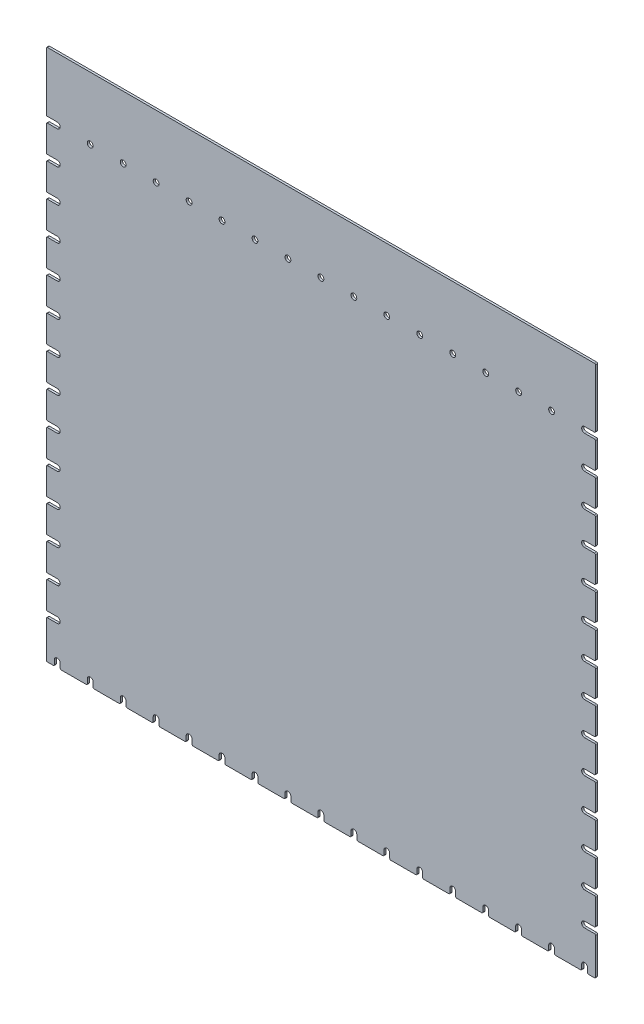
SolidWorks part; units mm, degrees
material "AISI 1045 Steel, cold drawn"
ref_plane "Front Plane" through (0, 0, 0) normal (0, 0, 1) x (1, 0, 0)
ref_plane "Top Plane" through (0, 0, 0) normal (0, 1, 0) x (1, 0, 0)
ref_plane "Right Plane" through (0, 0, 0) normal (1, 0, 0) x (0, 0, -1)
sketch "Sketch1" plane through (0, 0, 0) normal (0, 0, 1) x (1, 0, 0)
  line L1 (250, -242.265) -> (-250, -242.265)
  line L2 (250, -242.265) -> (250, 242.265)
  line L3 (250, 242.265) -> (-250, 242.265)
  line L4 (-250, -242.265) -> (-250, 242.265)
  line L5 (250, -242.265) -> (-250, 242.265) construction
  line L6 (250, 242.265) -> (-250, -242.265) construction
  point P0 (0, 0)
  dimension "D1" = 500
  dimension "D2" = 484.53
extrude "Boss-Extrude1" add sketch "Sketch1" along normal mid plane 2
hole_wizard "M5 Clearance Hole2" positions "Sketch2" profile "Sketch3" hole size "M5" standard "ANSI Metric"
sketch "Sketch2" plane through (0, 0, 1) normal (0, 0, 1) x (1, 0, 0)
  line L1 (240, -237.265) -> (-240, -237.265)
  line L2 (240, -237.265) -> (240, 185.265)
  line L3 (240, 185.265) -> (-240, 185.265)
  line L4 (-240, -237.265) -> (-240, 185.265)
  line L5 (240, -237.265) -> (-240, 185.265) construction
  line L6 (240, 185.265) -> (-240, -237.265) construction
  line L7 (-250, -242.265) -> (250, -242.265) construction
  line L8 (-250, 242.265) -> (-250, -242.265) construction
  line L9 (0, -26) -> (0, -237.265) construction
  point P137 (-240, -237.265)
  point P142 (0, -26)
  dimension "D1" = 5
  dimension "D2" = 10
  dimension "D3" = 427.53
sketch "Sketch3" plane through (-240, -237.265, 1) normal (1, 0, 0) x (0, -1, 0)
  line L0 (0, 0) -> (0, 9.5923)
  line L1 (0, 9.5923) -> (2.65, 8)
  line L2 (2.65, 8) -> (2.65, 0)
  line L5 (2.65, 0) -> (0, 0)
  line L10 (0, 9.5923) -> (-2.65, 8) construction
  line L11 (0, -6.35) -> (0, 107.95) construction
  dimension "Hole Dia." = 5.3
  dimension "Hole Depth" = 8
  dimension "Drill Angle" = 118
sketch "Sketch4" plane through (0, 0, 1) normal (0, 0, 1) x (1, 0, 0)
  line L0 (-242.65, -237.265) -> (-242.65, -242.265)
  line L1 (-250, -242.265) -> (250, -242.265) construction
  line L2 (-242.65, -242.265) -> (-237.35, -242.265)
  line L3 (-237.35, -242.265) -> (-237.35, -237.265)
  circle A0 centre (-240, -237.265) radius 2.65 construction
  arc A1 (-242.65, -237.265) -> (-237.35, -237.265) centre (-240, -237.265) ccw
  point P9 (-242.1, -237.265)
  point P10 (-237.9, -237.265)
extrude "Cut-Extrude1" cut sketch "Sketch4" against normal up to surface (2 mm away) up to face at (-237.35, -237.265, -1)
pattern_linear "LPattern1" count 17 spacing 30 along (1, 0, 0) of "Cut-Extrude1", "M5 Clearance Hole2"
fillet "Fillet1" radius 1 34 edges at (-182.65, -242.265, 0) (-177.35, -242.265, 0) (-152.65, -242.265, 0) (-147.35, -242.265, 0) (-122.65, -242.265, 0) (-117.35, -242.265, 0) (-92.65, -242.265, 0) (-87.35, -242.265, 0) (-62.65, -242.265, 0) (-57.35, -242.265, 0) (-32.65, -242.265, 0) (-27.35, -242.265, 0) (-2.65, -242.265, 0) (2.65, -242.265, 0) (27.35, -242.265, 0) (32.65, -242.265, 0) (57.35, -242.265, 0) (62.65, -242.265, 0) (87.35, -242.265, 0) (92.65, -242.265, 0) (117.35, -242.265, 0) (122.65, -242.265, 0) (147.35, -242.265, 0) (152.65, -242.265, 0) (177.35, -242.265, 0) (182.65, -242.265, 0) (207.35, -242.265, 0) (212.65, -242.265, 0) (237.35, -242.265, 0) (242.65, -242.265, 0) (-237.35, -242.265, 0) (-212.65, -242.265, 0) (-207.35, -242.265, 0) (-242.65, -242.265, 0)
hole_wizard "M5 Clearance Hole1" positions "Sketch5" profile "Sketch6" hole size "M5" standard "ANSI Metric"
sketch "Sketch5" plane through (0, 0, 1) normal (0, 0, 1) x (1, 0, 0)
  point P0 (-240, 185.265)
sketch "Sketch6" plane through (-240, 185.265, 1) normal (1, 0, 0) x (0, -1, 0)
  line L0 (0, 0) -> (0, 9.5923)
  line L1 (0, 9.5923) -> (2.65, 8)
  line L2 (2.65, 8) -> (2.65, 0)
  line L5 (2.65, 0) -> (0, 0)
  line L10 (0, 9.5923) -> (-2.65, 8) construction
  line L11 (0, -6.35) -> (0, 107.95) construction
  dimension "Hole Dia." = 5.3
  dimension "Hole Depth" = 8
  dimension "Drill Angle" = 118
pattern_linear "LPattern2" count 17 spacing 30 along (1, 0, 0) of "M5 Clearance Hole1"
sketch "Sketch7" plane through (0, 0, 1) normal (0, 0, 1) x (1, 0, 0)
  line L0 (-240, 187.915) -> (-250, 187.915)
  line L1 (-250, 242.265) -> (-250, -242.265) construction
  line L2 (-250, 187.915) -> (-250, 182.615)
  line L3 (-250, 182.615) -> (-240, 182.615)
  circle A0 centre (-240, 185.265) radius 2.65 construction
  arc A1 (-240, 187.915) -> (-240, 182.615) centre (-240, 185.265) ccw
  point P6 (-240, 187.915)
  point P9 (-240, 182.615)
  point P10 (0, 0)
extrude "Cut-Extrude2" cut sketch "Sketch7" against normal up to surface (2 mm away) up to face at (-207.35, 185.265, -1)
pattern_linear "LPattern3" count 14 spacing 30 along (0, -1, 0) of "M5 Clearance Hole1", "Cut-Extrude2"
mirror "Mirror1" about plane through (0, 0, 0) normal (1, 0, 0) of "LPattern3"
fillet "Fillet2" radius 1 60 edges at (250, 187.915, 0) (250, 242.265, 0) (-250, 242.265, 0) (-250, 182.615, 0) (-250, 157.915, 0) (-250, 152.615, 0) (-250, 127.915, 0) (-250, 122.615, 0) (-250, 97.915, 0) (-250, 92.615, 0) (-250, 67.915, 0) (-250, 62.615, 0) (-250, 37.915, 0) (-250, 32.615, 0) (-250, 7.915, 0) (-250, 2.615, 0) (-250, -22.085, 0) (-250, -27.385, 0) (-250, -52.085, 0) (-250, -57.385, 0) (-250, -82.085, 0) (-250, -87.385, 0) (-250, -112.085, 0) (-250, -117.385, 0) (-250, -142.085, 0) (-250, -147.385, 0) (-250, -172.085, 0) (-250, -177.385, 0) (-250, -202.085, 0) (-250, -207.385, 0) (-250, -242.265, 0) (250, -242.265, 0) (250, -207.385, 0) (250, -202.085, 0) (250, -177.385, 0) (250, -172.085, 0) (250, -147.385, 0) (250, -142.085, 0) (250, -117.385, 0) (250, -112.085, 0) (250, -87.385, 0) (250, -82.085, 0) (250, -57.385, 0) (250, -52.085, 0) (250, -27.385, 0) (250, -22.085, 0) (250, 2.615, 0) (250, 7.915, 0) (250, 32.615, 0) (250, 37.915, 0) (250, 62.615, 0) (250, 67.915, 0) (250, 92.615, 0) (250, 97.915, 0) (250, 122.615, 0) (250, 127.915, 0) (250, 152.615, 0) (250, 157.915, 0) (250, 182.615, 0) (-250, 187.915, 0)
